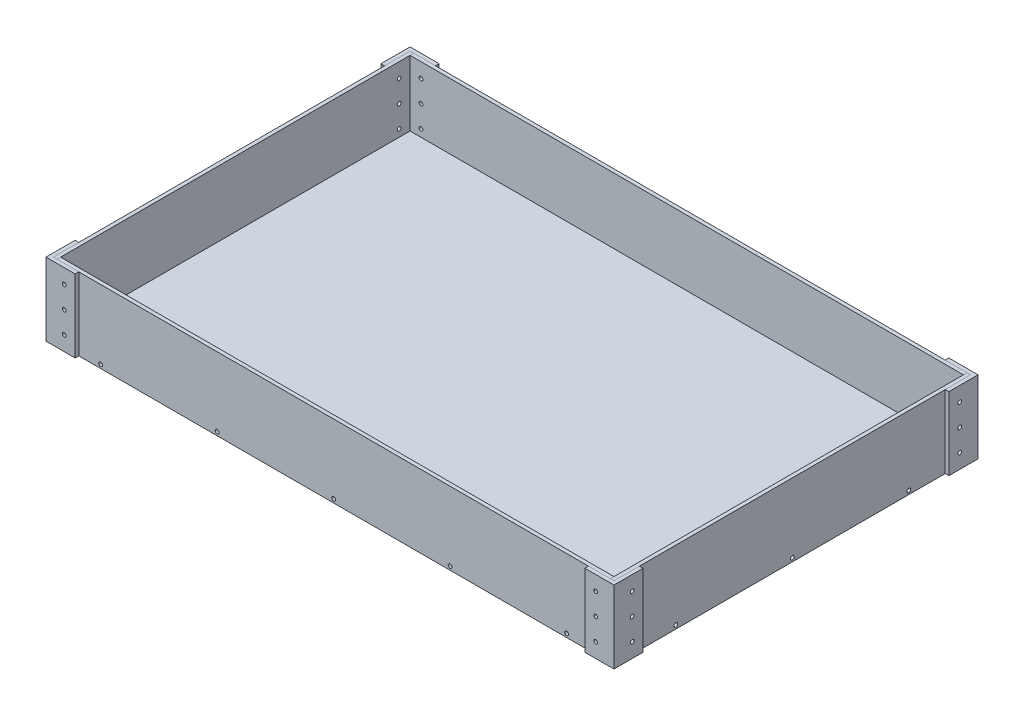
SolidWorks part; units mm, degrees
ref_plane "Front" through (0, 0, 0) normal (0, 0, 1) x (1, 0, 0)
ref_plane "Top" through (0, 0, 0) normal (0, 1, 0) x (1, 0, 0)
ref_plane "Right" through (0, 0, 0) normal (1, 0, 0) x (0, 0, -1)
sketch "Sketch1" plane through (0, 0, 0) normal (0, 1, 0) x (1, 0, 0)
  line L1 (-241.3, 152.4) -> (241.3, 152.4)
  line L2 (-241.3, 152.4) -> (-241.3, -152.4)
  line L3 (-241.3, -152.4) -> (241.3, -152.4)
  line L4 (241.3, 152.4) -> (241.3, -152.4)
  line L5 (-241.3, 152.4) -> (241.3, -152.4) construction
  line L6 (-241.3, -152.4) -> (241.3, 152.4) construction
  point P0 (0, 0)
  dimension "D1" = 482.6
  dimension "D2" = 304.8
extrude "Boss-Extrude1" add sketch "Sketch1" along normal blind 6.35
sketch "Sketch2" plane through (0, 6.35, 0) normal (0, 1, 0) x (1, 0, 0)
  line L0 (241.3, -152.4) -> (241.3, 152.4) construction
  line L1 (-241.3, 152.4) -> (241.3, 152.4)
  line L2 (-241.3, 152.4) -> (-241.3, 155.575)
  line L3 (-241.3, 155.575) -> (241.3, 155.575)
  line L4 (241.3, 152.4) -> (241.3, 155.575)
  line L5 (-241.3, 152.4) -> (241.3, 155.575) construction
  line L6 (-241.3, 155.575) -> (241.3, 152.4) construction
  line L7 (-241.3, -155.575) -> (241.3, -155.575)
  line L8 (-241.3, -155.575) -> (-241.3, -152.4)
  line L9 (-241.3, -152.4) -> (241.3, -152.4)
  line L10 (241.3, -155.575) -> (241.3, -152.4)
  line L11 (-241.3, -155.575) -> (241.3, -152.4) construction
  line L12 (-241.3, -152.4) -> (241.3, -155.575) construction
  line L13 (-241.3, 152.4) -> (-241.3, -152.4) construction
  line L14 (241.3, 152.4) -> (-241.3, 152.4) construction
  line L15 (-241.3, -152.4) -> (241.3, -152.4) construction
  point P0 (0, 153.9875)
  point P5 (0, -153.9875)
  dimension "D1" = 3.175
extrude "Boss-Extrude2" add sketch "Sketch2" along normal blind 57.15 and the other way up to surface (6.35 mm away) separate body other way up to face at (0, 0, 0)
sketch "Sketch3" plane through (0, 6.35, 0) normal (0, 1, 0) x (1, 0, 0)
  line L0 (241.3, -155.575) -> (-241.3, -155.575) construction
  line L1 (-241.3, 155.575) -> (-244.475, 155.575)
  line L2 (-241.3, 155.575) -> (-241.3, -155.575)
  line L3 (-241.3, -155.575) -> (-244.475, -155.575)
  line L4 (-244.475, 155.575) -> (-244.475, -155.575)
  line L6 (241.3, 155.575) -> (244.475, 155.575)
  line L7 (241.3, 155.575) -> (241.3, -155.575)
  line L8 (241.3, -155.575) -> (244.475, -155.575)
  line L9 (244.475, 155.575) -> (244.475, -155.575)
  dimension "D1" = 3.175
extrude "Boss-Extrude3" add sketch "Sketch3" along normal up to surface (57.15 mm away) and the other way up to surface (6.35 mm away) separate body up to face at (0, 63.5, -153.9875) other way up to face at (0, 0, 0)
sketch "Sketch4" plane through (0, 0, 0) normal (0, -1, 0) x (1, 0, 0)
  line L0 (-244.475, -155.575) -> (-222.25, -155.575)
  line L2 (-222.25, -155.575) -> (-222.25, -158.75)
  line L3 (-222.25, -158.75) -> (-247.65, -158.75)
  line L4 (-247.65, -158.75) -> (-247.65, -133.35)
  line L5 (-247.65, -133.35) -> (-244.475, -133.35)
  line L7 (-244.475, -133.35) -> (-244.475, -155.575)
  line L8 (-244.475, 155.575) -> (-244.475, -155.575) construction
  line L9 (-241.3, -155.575) -> (241.3, -155.575) construction
  dimension "D1" = 3.175
  dimension "D2" = 25.4
  dimension "D3" = 25.4
extrude "Boss-Extrude4" add sketch "Sketch4" against normal up to surface (63.5 mm away) separate body up to face at (0, 63.5, -153.9875)
mirror "Mirror1" about plane through (0, 0, 0) normal (1, 0, 0) of bodies 184
mirror "Mirror2" about plane through (0, 0, 0) normal (0, 0, 1) of bodies 184 185
sketch "Sketch5" plane through (0, 0, -155.575) normal (0, 0, -1) x (-1, 0, 0)
  line L0 (-241.3, 31.75) -> (-222.25, 31.75) construction
  line L1 (-241.3, 0) -> (-241.3, 63.5) construction
  line L2 (-222.25, 63.5) -> (-222.25, 0) construction
  line L3 (-231.775, 50.8) -> (-231.775, 12.7) construction
  circle A0 centre (-231.775, 50.8) radius 1.651
  circle A1 centre (-231.775, 31.75) radius 1.651
  circle A2 centre (-231.775, 12.7) radius 1.651
  point P8 (-231.775, 31.75)
  dimension "D2" = 3.302
  dimension "D1" = 38.1
extrude "Cut-Extrude1" cut sketch "Sketch5" against normal through all
mirror "Mirror3" about plane through (0, 0, 0) normal (1, 0, 0) of "Cut-Extrude1"
sketch "Sketch6" plane through (-247.65, 0, 0) normal (-1, 0, 0) x (0, 0, 1)
  line L0 (-152.4, 31.75) -> (-133.35, 31.75) construction
  line L1 (-133.35, 63.5) -> (-133.35, 0) construction
  line L2 (-152.4, 0) -> (-152.4, 63.5) construction
  line L3 (-142.875, 50.8) -> (-142.875, 12.7) construction
  circle A0 centre (-142.875, 50.8) radius 1.651
  circle A1 centre (-142.875, 31.75) radius 1.651
  circle A2 centre (-142.875, 12.7) radius 1.651
  point P2 (-142.875, 31.75)
  point P5 (-142.875, 31.75)
  dimension "D2" = 3.302
  dimension "D1" = 38.1
extrude "Cut-Extrude2" cut sketch "Sketch6" against normal through all
mirror "Mirror4" about plane through (0, 0, 0) normal (0, 0, 1) of "Cut-Extrude2"
sketch "Sketch7" plane through (0, 0, 155.575) normal (0, 0, 1) x (1, 0, 0)
  line L0 (-247.65, 3.175) -> (247.65, 3.175) construction
  line L1 (-247.65, 6.35) -> (-247.65, 0) construction
  line L2 (241.3, 0) -> (-241.3, 0) construction
  line L3 (-241.3, 6.35) -> (241.3, 6.35) construction
  line L4 (247.65, 63.5) -> (247.65, 0) construction
  circle A0 centre (-203.2, 3.175) radius 1.651
  circle A1 centre (0, 3.175) radius 1.651
  circle A2 centre (203.2, 3.175) radius 1.651
  circle A3 centre (101.6, 3.175) radius 1.651
  circle A4 centre (-101.6, 3.175) radius 1.651
  dimension "D1" = 3.302
  dimension "D3" = 3.302
  dimension "D4" = 101.6
  dimension "D5" = 101.6
  dimension "D6" = 203.2
  dimension "D2" = 203.2
extrude "Cut-Extrude3" cut sketch "Sketch7" against normal through all and the other way through all
sketch "Sketch8" plane through (244.475, 0, 0) normal (1, 0, 0) x (0, 0, -1)
  line L0 (-158.75, 3.175) -> (158.75, 3.175) construction
  line L1 (-158.75, 63.5) -> (-158.75, 0) construction
  line L2 (158.75, 63.5) -> (158.75, 0) construction
  line L3 (0, 0) -> (0, 6.35) construction
  line L4 (-152.4, 6.35) -> (152.4, 6.35) construction
  circle A0 centre (0, 3.175) radius 1.651
  circle A1 centre (101.6, 3.175) radius 1.651
  circle A2 centre (-101.6, 3.175) radius 1.651
  point P12 (0, 3.175)
  dimension "D1" = 3.302
  dimension "D2" = 101.6
  dimension "D3" = 101.6
extrude "Cut-Extrude4" cut sketch "Sketch8" against normal through all
